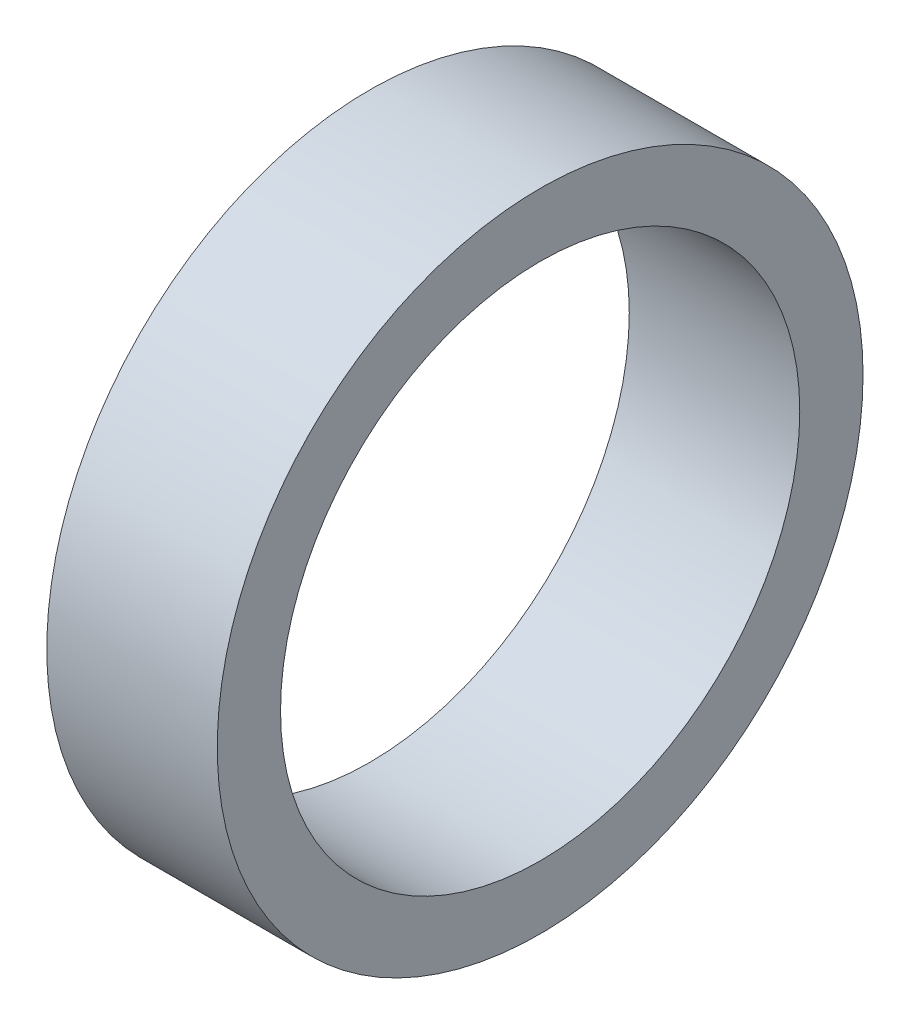
SolidWorks part; units mm, degrees
material "DELRIN (WHITE)"
ref_plane "Front" through (0, 0, 0) normal (0, 0, 1) x (1, 0, 0)
ref_plane "Top" through (0, 0, 0) normal (0, 1, 0) x (1, 0, 0)
ref_plane "Right" through (0, 0, 0) normal (1, 0, 0) x (0, 0, -1)
ref_axis "Axis1" through (0, 50, 0) along (0, -1, 0)
sketch "Sketch1" plane through (0, 0, 0) normal (1, 0, 0) x (0, 0, -1)
  circle A0 centre (0, 0) radius 15.875
  dimension "D1" = 31.75
extrude "Boss-Extrude1" add sketch "Sketch1" along normal blind 8.382
sketch "Sketch2" plane through (8.382, 0, 0) normal (1, 0, 0) x (0, 0, -1)
  circle A0 centre (0, 0) radius 12.7635
  dimension "D1" = 25.527
extrude "Cut-Extrude1" cut sketch "Sketch2" against normal up to next
